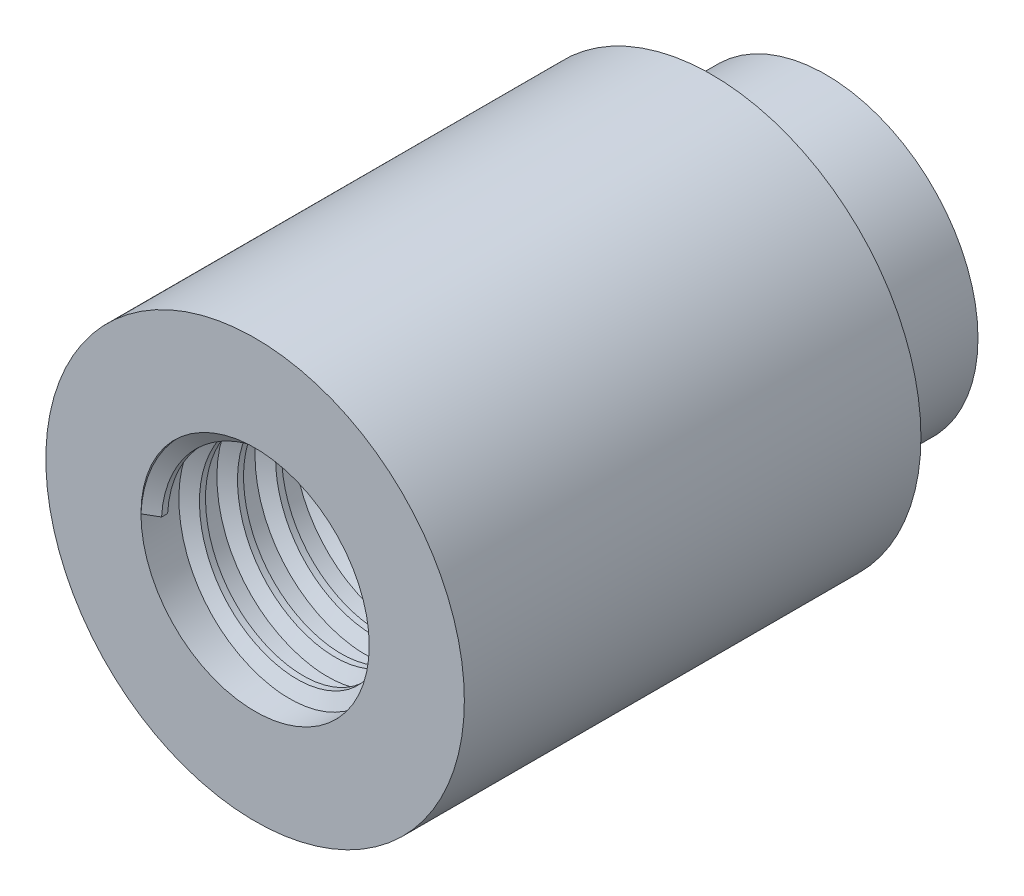
SolidWorks part; units mm, degrees
ref_plane "前视基准面" through (0, 0, 0) normal (0, 0, 1) x (1, 0, 0)
ref_plane "上视基准面" through (0, 0, 0) normal (0, 1, 0) x (1, 0, 0)
ref_plane "右视基准面" through (0, 0, 0) normal (1, 0, 0) x (0, 0, -1)
other "Configuration Table"
sketch "草图1" plane through (0, 0, 121.6176) normal (0, 0, 1) x (1, 0, 0)
  circle A0 centre (-65.0658, 36.048) radius 2
  circle A1 centre (-65.0658, 36.048) radius 1.5
  dimension "D1" = 4
  dimension "D2" = 3
extrude "凸台-拉伸1" add sketch "草图1" against normal blind 1.5
sketch "草图2" plane through (0, 0, 121.6176) normal (0, 0, 1) x (1, 0, 0)
  circle A0 centre (-65.0658, 36.048) radius 1.5
  circle A1 centre (-65.0658, 36.048) radius 2.75
  dimension "D1" = 5.5
extrude "凸台-拉伸2" add sketch "草图2" along normal blind 6
thread "螺纹线1" pitch 0.3175 method extrude profile "螺纹线轮廓1" start angle 0, offset 0, length 7.5, pitch 0.5, diameter 3
ref_plane "基准面1" through (-66.5658, 36.048, 127.6176) normal (0, -1, 0) x (-1, 0, 0)
sketch "螺纹线轮廓1" plane through (-66.5658, 36.048, 127.6176) normal (0, -1, 0) x (-1, 0, 0)
  line L0 (0, 0) -> (0, 0.3175) construction
  line L11 (0, 0) -> (0, 0.2778)
  line L12 (0, 0.2778) -> (-0.1719, 0.1786)
  line L13 (-0.1719, 0.1786) -> (-0.1719, 0.0992)
  line L15 (-0.1719, 0.0992) -> (0, 0)
  line L17 (-0.1719, 0.1389) -> (0, 0.1389) construction
  point P2 (0, 0)
  dimension "Pitch" = 0.3175
  dimension "Profile_Angle" = 60
  dimension "Profile_Land" = 0.0794
  dimension "Profile_Height" = 0.1719
